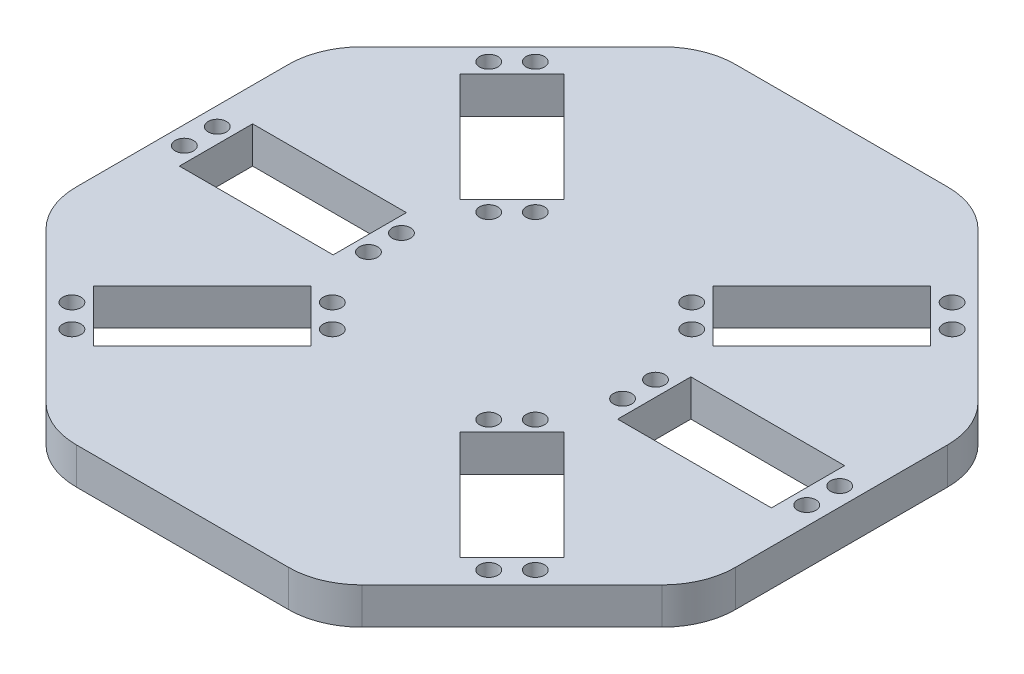
SolidWorks part; units mm, degrees
ref_plane "Front Plane" through (0, 0, 0) normal (0, 0, 1) x (1, 0, 0)
ref_plane "Top Plane" through (0, 0, 0) normal (0, 1, 0) x (1, 0, 0)
ref_plane "Right Plane" through (0, 0, 0) normal (1, 0, 0) x (0, 0, -1)
sketch "Sketch1" plane through (0, 0, 0) normal (0, 1, 0) x (1, 0, 0)
  line L0 (21.3546, -27.7186) -> (56.9221, -63.2861)
  line L1 (-90, -37.2792) -> (-37.2792, -90)
  line L2 (-37.2792, -90) -> (37.2792, -90)
  line L3 (37.2792, -90) -> (90, -37.2792)
  line L4 (90, -37.2792) -> (90, 37.2792)
  line L5 (90, 37.2792) -> (37.2792, 90)
  line L6 (37.2792, 90) -> (-37.2792, 90)
  line L7 (-37.2792, 90) -> (-90, 37.2792)
  line L8 (-90, 37.2792) -> (-90, -37.2792)
  line L9 (21.3546, -27.7186) -> (27.7186, -21.3546)
  line L10 (56.9221, -63.2861) -> (63.2861, -56.9221)
  line L11 (27.7186, -21.3546) -> (63.2861, -56.9221)
  line L12 (63.6396, -63.6396) -> (0, 0) construction
  line L13 (34.5422, -20.4) -> (20.4, -34.5422)
  line L14 (34.5422, -20.4) -> (64.2407, -50.0985)
  line L15 (20.4, -34.5422) -> (50.0985, -64.2407)
  line L16 (64.2407, -50.0985) -> (50.0985, -64.2407)
  line L17 (10, -38.85) -> (-10, -38.85) [skipped]
  line L18 (10, -38.85) -> (10, -80.85) [skipped]
  line L19 (10, -80.85) -> (-10, -80.85) [skipped]
  line L20 (-10, -38.85) -> (-10, -80.85) [skipped]
  line L21 (-20.4, -34.5422) -> (-34.5422, -20.4)
  line L22 (-20.4, -34.5422) -> (-50.0985, -64.2407)
  line L23 (-50.0985, -64.2407) -> (-64.2407, -50.0985)
  line L24 (-34.5422, -20.4) -> (-64.2407, -50.0985)
  line L25 (-38.85, -10) -> (-38.85, 10)
  line L26 (-38.85, -10) -> (-80.85, -10)
  line L27 (-80.85, -10) -> (-80.85, 10)
  line L28 (-38.85, 10) -> (-80.85, 10)
  line L29 (-34.5422, 20.4) -> (-20.4, 34.5422)
  line L30 (-34.5422, 20.4) -> (-64.2407, 50.0985)
  line L31 (-64.2407, 50.0985) -> (-50.0985, 64.2407)
  line L32 (-20.4, 34.5422) -> (-50.0985, 64.2407)
  line L33 (-10, 38.85) -> (10, 38.85) [skipped]
  line L34 (-10, 38.85) -> (-10, 80.85) [skipped]
  line L35 (-10, 80.85) -> (10, 80.85) [skipped]
  line L36 (10, 38.85) -> (10, 80.85) [skipped]
  line L37 (20.4, 34.5422) -> (34.5422, 20.4)
  line L38 (20.4, 34.5422) -> (50.0985, 64.2407)
  line L39 (50.0985, 64.2407) -> (64.2407, 50.0985)
  line L40 (34.5422, 20.4) -> (64.2407, 50.0985)
  line L41 (38.85, 10) -> (38.85, -10)
  line L42 (38.85, 10) -> (80.85, 10)
  line L43 (80.85, 10) -> (80.85, -10)
  line L44 (38.85, -10) -> (80.85, -10)
  circle A0 centre (0, 0) radius 90 construction
  circle A5 centre (56.9221, -63.2861) radius 2.5
  circle A6 centre (63.2861, -56.9221) radius 2.5
  circle A7 centre (27.7186, -21.3546) radius 2.5
  circle A8 centre (21.3546, -27.7186) radius 2.5
  circle A9 centre (-4.5, -34.7) radius 2.5 [skipped]
  circle A10 centre (4.5, -34.7) radius 2.5 [skipped]
  circle A11 centre (4.5, -85) radius 2.5 [skipped]
  circle A12 centre (-4.5, -85) radius 2.5 [skipped]
  circle A13 centre (0, 0) radius 90 construction
  circle A14 centre (-27.7186, -21.3546) radius 2.5
  circle A15 centre (-21.3546, -27.7186) radius 2.5
  circle A16 centre (-56.9221, -63.2861) radius 2.5
  circle A17 centre (-63.2861, -56.9221) radius 2.5
  circle A18 centre (0, 0) radius 90 construction
  circle A19 centre (-34.7, 4.5) radius 2.5
  circle A20 centre (-34.7, -4.5) radius 2.5
  circle A21 centre (-85, -4.5) radius 2.5
  circle A22 centre (-85, 4.5) radius 2.5
  circle A23 centre (0, 0) radius 90 construction
  circle A24 centre (-21.3546, 27.7186) radius 2.5
  circle A25 centre (-27.7186, 21.3546) radius 2.5
  circle A26 centre (-63.2861, 56.9221) radius 2.5
  circle A27 centre (-56.9221, 63.2861) radius 2.5
  circle A28 centre (0, 0) radius 90 construction
  circle A29 centre (4.5, 34.7) radius 2.5 [skipped]
  circle A30 centre (-4.5, 34.7) radius 2.5 [skipped]
  circle A31 centre (-4.5, 85) radius 2.5 [skipped]
  circle A32 centre (4.5, 85) radius 2.5 [skipped]
  circle A33 centre (0, 0) radius 90 construction
  circle A34 centre (27.7186, 21.3546) radius 2.5
  circle A35 centre (21.3546, 27.7186) radius 2.5
  circle A36 centre (56.9221, 63.2861) radius 2.5
  circle A37 centre (63.2861, 56.9221) radius 2.5
  circle A38 centre (0, 0) radius 90 construction
  circle A39 centre (34.7, -4.5) radius 2.5
  circle A40 centre (34.7, 4.5) radius 2.5
  circle A41 centre (85, 4.5) radius 2.5
  circle A42 centre (85, -4.5) radius 2.5
  circle A43 centre (0, 0) radius 90 construction
  point P15 (63.6396, -63.6396)
  point P16 (60.1041, -60.1041)
  point P17 (57.1696, -57.1696)
  point P121 (0, 0)
  dimension "D4" = 5
  dimension "D5" = 5
  dimension "D6" = 5
  dimension "D7" = 5
  dimension "D1" = 90
  dimension "D2" = 9
  dimension "D3" = 50.3
  dimension "D8" = 5
  dimension "D9" = 42
  dimension "D10" = 20
  dimension "D11" = 4.15
  dimension "D12" = 8
extrude "Boss-Extrude1" add sketch "Sketch1" along normal blind 10 contours L11 A7 L9 | L9 A7 L11 | L9 A8 L0 | L0 A8 L9 | L11 A6 L10 | L10 A6 L11 | L10 A5 L0 | L0 A5 L10 | L16 L14 L13 L11 | L16 L11 L13 L0 | L16 L0 L13 L15 | L37 L40 L39 L38 | L41 L44 L43 L42 | L29 L32 L31 L30 | L25 L28 L27 L26 | L21 L24 L23 L22 | A22 | A21 | A19 | A20 | A26 | A27 | A24 | A25 | A35 | A34 | A40 | A39 | A41 | A42 | A17 | A16 | A14 | A36 | A37 | L8 L1 L2 L3 L4 L5 L6 L7 | A15 region at (22.8552, 0, 27.7186) region at (20.8544, 0, 27.7186) region at (42.3203, 0, 42.3203) region at (37.1938, 0, 47.4469) region at (27.7186, 0, 20.8544) region at (27.7186, 0, 22.8552) region at (47.4469, 0, 37.1938) region at (56.9221, 0, 61.7855) region at (56.9221, 0, 63.7862) region at (63.7862, 0, 56.9221) region at (61.7855, 0, 56.9221) region at (-42.3203, 0, 42.3203) region at (-59.85, 0, 0) region at (-42.3203, 0, -42.3203) region at (42.3203, 0, -42.3203) region at (59.85, 0, 0) region at (-27.7186, 0, 21.3546) region at (-56.9221, 0, 63.2861) region at (-63.2861, 0, 56.9221) region at (-34.7, 0, -4.5) region at (-34.7, 0, 4.5) region at (-85, 0, 4.5) region at (-85, 0, -4.5) region at (-21.3546, 0, -27.7186) region at (-27.7186, 0, -21.3546) region at (-63.2861, 0, -56.9221) region at (-56.9221, 0, -63.2861) region at (27.7186, 0, -21.3546) region at (21.3546, 0, -27.7186) region at (56.9221, 0, -63.2861) region at (63.2861, 0, -56.9221) region at (34.7, 0, 4.5) region at (34.7, 0, -4.5) region at (85, 0, -4.5) region at (85, 0, 4.5)
fillet "Fillet1" radius 20 8 edges at (-90, 5, -37.2792) (-37.2792, 5, -90) (37.2792, 5, -90) (90, 5, -37.2792) (90, 5, 37.2792) (37.2792, 5, 90) (-37.2792, 5, 90) (-90, 5, 37.2792)
